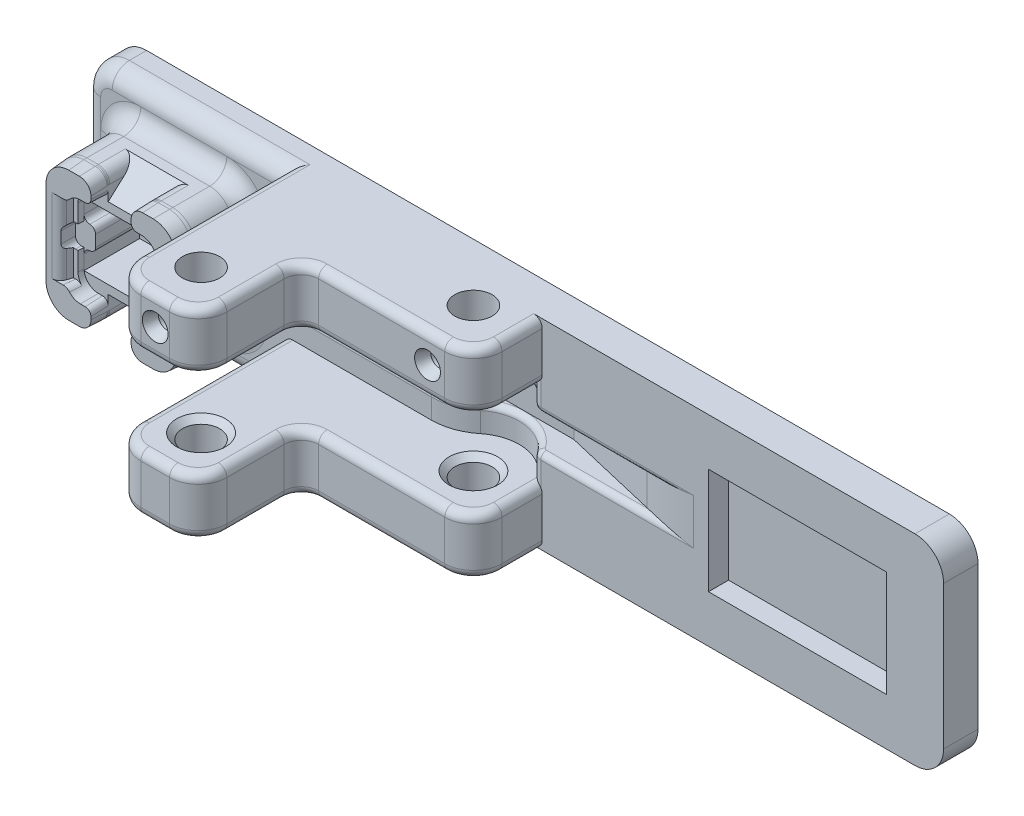
SolidWorks part; units mm, degrees
ref_plane "Top Plane" through (0, 0, 0) normal (0, 0, 1) x (1, 0, 0)
ref_plane "Right Plane" through (0, 0, 0) normal (0, 1, 0) x (1, 0, 0)
ref_plane "Front Plane" through (0, 0, 0) normal (1, 0, 0) x (0, 0, -1)
sketch "Sketch1" plane through (0, 0, 0) normal (0, 0, 1) x (1, 0, 0)
  line L0 (15, 2.5) -> (15, 6.45) construction
  line L1 (12.5, 15) -> (8.55, 15) construction
  line L2 (0, 6.45) -> (0, 2.5) construction
  line L3 (2.5, 0) -> (6.45, 0) construction
  line L4 (15, 2.5) -> (15, 6.45) construction
  line L5 (12.5, 15) -> (8.55, 15) construction
  line L6 (0, 6.45) -> (0, 2.5) construction
  line L7 (2.5, 0) -> (6.45, 0) construction
  line L8 (0, 0) -> (15, 15) construction
  line L9 (0, 0) -> (15, 0) construction
  line L10 (0, 0) -> (0, 15) construction
  line L11 (0, 15) -> (15, 15) construction
  line L12 (15, 0) -> (15, 15) construction
  line L14 (140, 25) -> (-10, 25)
  line L15 (140, 25) -> (140, -10)
  line L16 (140, -10) -> (-10, -10)
  line L17 (-10, 25) -> (-10, -10)
  circle A0 centre (14.2188, 11.3651) radius 0.5 construction
  circle A1 centre (14.2188, 3.6349) radius 0.5 construction
  circle A2 centre (7, 4) radius 0.5 construction
  circle A3 centre (4, 5.9999) radius 0.5 construction
  circle A4 centre (4, 9) radius 0.5 construction
  circle A5 centre (0.7812, 11.3651) radius 0.5 construction
  circle A6 centre (0.7812, 3.6349) radius 0.5 construction
  circle A7 centre (14.2188, 11.3651) radius 0.5
  circle A8 centre (14.2188, 3.6349) radius 0.5
  circle A9 centre (7, 4) radius 0.5
  circle A10 centre (4, 5.9999) radius 0.5
  circle A11 centre (4, 9) radius 0.5
  circle A12 centre (0.7812, 11.3651) radius 0.5
  circle A13 centre (0.7812, 3.6349) radius 0.5
  dimension "D1" = 10
  dimension "D2" = 10
  dimension "D3" = 10
  dimension "D4" = 125
extrude "Boss-Extrude1" add sketch "Sketch1" along normal blind 4 contours L15 L14 L17 L16
sketch "Sketch2" plane through (0, 0, 4) normal (0, 0, 1) x (1, 0, 0)
  line L0 (0, 0) -> (15, 15) construction
  line L1 (0, 15) -> (15, 15) construction
  line L2 (0, 15) -> (0, 0) construction
  line L3 (0, 0) -> (15, 0) construction
  line L4 (15, 15) -> (15, 0) construction
  line L5 (19, -4) -> (-4, -4)
  line L6 (19, -4) -> (19, 19)
  line L7 (19, 19) -> (-4, 19)
  line L8 (-4, -4) -> (-4, 19)
  line L9 (19, -4) -> (-4, 19) construction
  line L10 (19, 19) -> (-4, -4) construction
  line L11 (-0.2, 13) -> (-0.2, 9.5)
  line L13 (15.2, 13) -> (15.2, 9.5)
  line L15 (-0.2, 13) -> (15.2, 13)
  line L16 (-0.2, 2) -> (15.2, 2)
  line L17 (7.5, 0) -> (7.5, 2) construction
  line L18 (7.5, 13) -> (7.5, 15) construction
  line L19 (1.8, 7.5) -> (13.2, 7.5) construction
  line L20 (-0.2, 5.5) -> (-0.2, 2)
  line L21 (1.8, 5.5) -> (-0.2, 5.5)
  line L22 (1.8, 5.5) -> (1.8, 9.5)
  line L23 (1.8, 9.5) -> (-0.2, 9.5)
  line L25 (1.8, 5.5) -> (-0.2, 9.5) construction
  line L26 (1.8, 9.5) -> (-0.2, 5.5) construction
  line L27 (13.2, 5.5) -> (15.2, 5.5)
  line L28 (13.2, 5.5) -> (13.2, 9.5)
  line L29 (13.2, 9.5) -> (15.2, 9.5)
  line L31 (13.2, 5.5) -> (15.2, 9.5) construction
  line L32 (13.2, 9.5) -> (15.2, 5.5) construction
  line L33 (15.2, 5.5) -> (15.2, 2)
  line L34 (-0.2, 15.2) -> (-0.2, -0.2) construction
  line L35 (-0.2, 15.2) -> (15.2, 15.2) construction
  line L36 (15.2, 15.2) -> (15.2, -0.2) construction
  line L37 (-0.2, -0.2) -> (15.2, -0.2) construction
  point P6 (7.5, 7.5)
  point P25 (0.8, 7.5)
  point P32 (14.2, 7.5)
  point P37 (-4, -4)
  point P38 (7.5, 7.5)
  point P39 (-4, -4)
  point P40 (-4, 19)
  point P41 (7.5, 7.5)
  point P42 (15.2, 6.1932)
  point P43 (17.8091, 7.5)
  point P44 (13.2, 7.5)
  point P45 (0, 0)
  point P46 (0, 0)
  point P47 (7.5, 7.5)
  point P48 (-4, -4)
  dimension "D1" = 4
  dimension "D3" = 2
  dimension "D4" = 2
  dimension "D5" = 4
  dimension "D2" = 0.2
extrude "Boss-Extrude2" add sketch "Sketch2" along normal blind 9.7
sketch "Sketch3" plane through (0, 0, 13.7) normal (0, 0, 1) x (1, 0, 0)
  line L0 (15.2, 15.2) -> (15.2, -0.2)
  line L1 (0, 15) -> (15, 15) construction
  line L2 (0, 15) -> (0, 0) construction
  line L3 (0, 0) -> (15, 0) construction
  line L4 (15, 15) -> (15, 0) construction
  line L5 (-0.2, -0.2) -> (15.2, -0.2)
  line L6 (-0.2, 15.2) -> (-0.2, -0.2)
  line L7 (-0.2, 15.2) -> (15.2, 15.2)
  line L9 (-4, 19) -> (19, 19)
  line L10 (-4, 19) -> (-4, -4)
  line L11 (-4, -4) -> (19, -4)
  line L12 (19, 19) -> (19, -4)
  dimension "D1" = 0.2
extrude "Boss-Extrude3" add sketch "Sketch3" along normal blind 3 draft 3
sketch "Sketch4" plane through (19, 0, 0) normal (1, 0, 0) x (0, 0, -1)
  line L0 (-13.7, 7.5) -> (-4, 7.5) construction
  line L1 (-13.7, -4) -> (-13.7, 19) construction
  line L2 (-4, -4) -> (-4, 19) construction
  line L3 (-4, -10) -> (-4, 25) construction
  line L4 (-8, 2.5) -> (-4, 2.5)
  line L5 (-8, 2.5) -> (-8, 12.5)
  line L6 (-8, 12.5) -> (-4, 12.5)
  line L7 (-4, 2.5) -> (-4, 12.5)
  line L8 (-8, 2.5) -> (-4, 12.5) construction
  line L9 (-8, 12.5) -> (-4, 2.5) construction
  point P6 (-6, 7.5)
  dimension "D1" = 4
  dimension "D2" = 10
extrude "Cut-Extrude1" cut sketch "Sketch4" against normal up to next
chamfer "Chamfer1" distance 2 angle 45 1 edges at (13.2, 7.5, 8)
chamfer "Chamfer2" distance 3 angle 45 2 edges at (17.1, 12.5, 8) (17.1, 2.5, 8)
fillet "Fillet1" radius 1 4 edges at (1.8, 9.5, 8.85) (1.8, 5.5, 8.85) (13.2, 5.5, 11.85) (13.2, 9.5, 11.85)
fillet "Fillet2" radius 1 4 edges at (-0.2, 5.5, 8.85) (-0.2, 9.5, 8.85) (15.2, 9.5, 10.85) (15.2, 5.5, 10.85)
fillet "Fillet3" radius 2.5 4 edges at (-0.2786, -0.2786, 15.2) (15.2786, -0.2786, 15.2) (-0.2786, 15.2786, 15.2) (15.2786, 15.2786, 15.2)
fillet "Fillet4" radius 10 4 edges at (19, 7.5, 13.7) (7.5, -4, 13.7) (7.5, 19, 13.7) (-4, 7.5, 13.7)
fillet "Fillet5" radius 4 12 edges at (19, 19, 8.7191) (18.9966, 18.9966, 13.6999) (19, -4, 8.7191) (18.9966, -3.9966, 13.6999) (-4, -4, 8.7191) (-3.9966, -3.9966, 13.6999) (-4, 19, 8.7191) (-3.9966, 18.9966, 13.6999) (18.9145, 18.9145, 15.3308) (18.9145, -3.9145, 15.3308) (-3.9145, -3.9145, 15.3308) (-3.9145, 18.9145, 15.3308)
sketch "Sketch5" plane through (0, 0, 16.7) normal (0, 0, 1) x (1, 0, 0)
  line L0 (12.7034, 15.2) -> (2.2966, 15.2) construction
  line L1 (15, 19) -> (0, 19) construction
  line L2 (12.7034, 15.2) -> (2.2966, 15.2) construction
  line L3 (15, 19) -> (0, 19) construction
  line L4 (7.5, 15.2) -> (7.5, 19) construction
  line L5 (1.8, 7.5) -> (13.2, 7.5) construction
  line L6 (11, 15.2) -> (4, 15.2)
  line L7 (11, 15.2) -> (11, 19)
  line L8 (11, 19) -> (4, 19)
  line L9 (4, 15.2) -> (4, 19)
  line L10 (11, 15.2) -> (4, 19) construction
  line L11 (11, 19) -> (4, 15.2) construction
  line L12 (1.8, 8.5) -> (1.8, 6.5) construction
  line L13 (13.2, 6.5) -> (13.2, 8.5) construction
  line L14 (7.5, 13) -> (7.5, 2) construction
  line L15 (15.2, 13) -> (-0.2, 13) construction
  line L16 (-0.1824, 2) -> (15.1824, 2) construction
  line L17 (-0.2, 10.5) -> (-0.2, 4.5) construction
  line L18 (15.2, 4.5) -> (15.2, 10.5) construction
  line L19 (-0.2, 10.5) -> (-0.2, 4.5)
  line L20 (15.2, 4.5) -> (15.2, 10.5)
  line L21 (-0.2, 7.5) -> (-4, 7.5) construction
  line L22 (-4, 15) -> (-4, 0) construction
  line L23 (15.2, 7.5) -> (18.8428, 7.5) construction
  line L24 (18.8428, 0.1517) -> (18.8428, 14.8483) construction
  line L25 (16.7, 5.5) -> (15.2, 5.5)
  line L26 (-1.7, 5.5) -> (-0.2, 5.5)
  line L27 (-1.7, 5.5) -> (-1.7, 9.5)
  line L28 (-1.7, 9.5) -> (-0.2, 9.5)
  line L29 (-0.2, 5.5) -> (-0.2, 9.5)
  line L30 (-1.7, 5.5) -> (-0.2, 9.5) construction
  line L31 (-1.7, 9.5) -> (-0.2, 5.5) construction
  line L32 (15.2, 5.5) -> (15.2, 9.5)
  line L33 (16.7, 9.5) -> (15.2, 9.5)
  line L34 (16.7, 5.5) -> (16.7, 9.5)
  line L35 (11, -0.2) -> (4, -0.2)
  line L36 (11, -0.2) -> (11, -4)
  line L37 (11, -4) -> (4, -4)
  line L38 (4, -0.2) -> (4, -4)
  point P6 (7.5, 17.1)
  point P35 (-0.95, 7.5)
  dimension "D1" = 7
  dimension "D2" = 4
  dimension "D3" = 1.5
extrude "Cut-Extrude2" cut sketch "Sketch5" against normal up to surface (3 mm away) contours L7 L8 L9 L6 | L33 L32 L25 L34 | L36 L37 L38 L35 | L26 L29 L28 L27 up to face at (7.5, 14.3355, 13.7)
fillet "Fillet6" radius 1 4 edges at (16.7, 9.5, 15.2) (16.7, 5.5, 15.2) (-1.7, 5.5, 15.2) (-1.7, 9.5, 15.2)
fillet "Fillet7" radius 2 8 edges at (4, 18.9923, 13.8308) (4, -3.9923, 13.8308) (11, -3.9923, 13.8308) (11, 18.9923, 13.8308) (4, 18.9145, 15.3308) (4, -3.9145, 15.3308) (11, -3.9145, 15.3308) (11, 18.9145, 15.3308)
fillet "Fillet8" radius 1 4 edges at (4, -0.2786, 15.2) (11, -0.2786, 15.2) (4, 15.2786, 15.2) (11, 15.2786, 15.2)
sketch "Sketch6" plane through (11, 0, 0) normal (-1, 0, 0) x (0, 0, 1)
  line L0 (4, 19) -> (13.4381, 19)
  line L1 (4, 19) -> (13.4381, 19) construction
  line L2 (4, 13) -> (13.7, 13)
  line L3 (4, 13) -> (13.7, 13) construction
  line L4 (13.7, 13) -> (13.7, 14.5) construction
  line L5 (13.7, 14.5) -> (8.7191, 19)
  line L6 (13.7, 14.5) -> (13.7, 19)
  line L7 (13.7, 19) -> (8.7191, 19)
  line L8 (8, 9.5) -> (8, 5.5) construction
  line L9 (8, 9.5) -> (8, 5.5)
  line L10 (8, 7.5) -> (14.4347, 7.5) construction
  line L11 (13.7, 0.5) -> (8.7191, -4)
  line L12 (13.7, -4) -> (8.7191, -4)
  line L13 (13.7, 0.5) -> (13.7, -4)
  dimension "D1" = 1.5
extrude "Cut-Extrude3" cut sketch "Sketch6" along normal up to surface (7 mm away) contours L5 L7 L6 | L13 L12 L11 up to face at (4, 16.677, 14.9314)
fillet "Fillet9" radius 2 8 edges at (4, -3.9991, 13.5691) (11, -3.9991, 13.5691) (4, 18.9991, 13.5691) (11, 18.9991, 13.5691) (4, -4, 11.0786) (11, -4, 11.0786) (4, 19, 11.0786) (11, 19, 11.0786)
sketch "Sketch7" plane through (0, 0, 0) normal (0, 0, -1) x (-1, 0, 0)
  line L4 (10, -10) -> (10, 25)
  line L5 (10, 25) -> (-140, 25)
  line L6 (-140, 25) -> (-140, -10)
  line L7 (-140, -10) -> (10, -10)
  line L8 (10, -10) -> (10, 25)
  line L9 (10, 25) -> (-140, 25)
  line L10 (-140, 25) -> (-140, -10)
  line L11 (-140, -10) -> (10, -10)
  dimension "D1" = 0
extrude "Boss-Extrude4" add sketch "Sketch7" along normal blind 1 contours L8 L9 L10 L11
fillet "Fillet10" radius 5 4 edges at (-10, -10, 1.5) (-10, 25, 1.5) (140, 25, 1.5) (140, -10, 1.5)
sketch "Sketch8" plane through (0, 0, 4) normal (0, 0, 1) x (1, 0, 0)
  line L0 (-10, 7.5) -> (140, 7.5) construction
  line L1 (-10, 20) -> (-10, -5) construction
  line L2 (140, -5) -> (140, 20) construction
  line L4 (99, -1.75) -> (130, -1.75)
  line L5 (99, -1.75) -> (99, 16.75)
  line L6 (99, 16.75) -> (130, 16.75)
  line L7 (130, -1.75) -> (130, 16.75)
  line L8 (99, -1.75) -> (130, 16.75) construction
  line L9 (99, 16.75) -> (130, -1.75) construction
  point P6 (114.5, 7.5)
  point P11 (0, 0)
  dimension "D1" = 31
  dimension "D2" = 10
  dimension "D3" = 18.5
extrude "Cut-Extrude4" cut sketch "Sketch8" against normal blind 3.5 contours L5 L4 L7 L6
ref_plane "Middle" through (0, 7.5, 0) normal (0, -1, 0) x (-1, 0, 0)
sketch "Sketch11" plane through (0, -10, 0) normal (0, -1, 0) x (1, 0, 0)
  line L0 (-5, 4) -> (135, 4) construction
  line L1 (25, 4) -> (36.8212, 4)
  line L2 (25, 4) -> (25, 34)
  line L3 (25, 34) -> (40, 34)
  line L4 (40, 16) -> (40, 34)
  line L5 (19, 13.4381) -> (19, 4) construction
  line L6 (40, 16) -> (70, 16)
  line L8 (36.8212, 4) -> (70, 4)
  line L9 (70, 16) -> (70, 4)
  line L10 (32.5, 34) -> (32.5, 4) construction
  line L11 (62, 16) -> (62, 4) construction
  circle A0 centre (32.5, 26) radius 3.25
  circle A1 centre (62, 8) radius 3.25
  dimension "D7" = 6.5
  dimension "D8" = 8
  dimension "D1" = 30
  dimension "D2" = 15
  dimension "D3" = 30
  dimension "D4" = 12
  dimension "D5" = 6
  dimension "D6" = 8
  dimension "D9" = 8
extrude "Boss-Extrude6" add sketch "Sketch11" against normal blind 10
mirror "Mirror1" about plane through (0, 7.5, 0) normal (0, -1, 0) of "Boss-Extrude6"
fillet "Fillet11" radius 5 6 edges at (70, -5, 16) (70, 20, 16) (25, -5, 34) (40, -5, 34) (40, 20, 34) (25, 20, 34)
fillet "Fillet12" radius 3 2 edges at (40, 20, 16) (40, -5, 16)
sketch "Sketch12" plane through (0, 15, 0) normal (0, -1, 0) x (1, 0, 0)
  line L0 (65, 16) -> (43, 16) construction
  circle A0 centre (62, 8) radius 8
extrude "Cut-Extrude5" cut sketch "Sketch12" along normal up to surface (15 mm away) up to face at (65.25, 0, 8)
fillet "Fillet13" radius 10 1 edges at (55.0718, 7.5, 4)
fillet "Fillet14" radius 1.5 1 edges at (68.9282, 7.5, 4)
fillet "Fillet15" radius 1.5 38 edges at (70, 0, 7.5) (70, -10, 7.5) (70, 15, 7.5) (70, 25, 7.5) (54, -10, 16) (32.5, -10, 34) (25, -10, 16.5) (38.5355, -10, 32.5355) (26.4645, -10, 32.5355) (68.5355, -10, 14.5355) (54, 0, 16) (25, 0, 16.5) (32.5, 0, 34) (38.5355, 0, 32.5355) (26.4645, 0, 32.5355) (68.5355, 0, 14.5355) (54, 25, 16) (54, 15, 16) (25, 25, 16.5) (32.5, 25, 34) (26.4645, 25, 32.5355) (38.5355, 25, 32.5355) (68.5355, 25, 14.5355) (25, 15, 16.5) (32.5, 15, 34) (26.4645, 15, 32.5355) (38.5355, 15, 32.5355) (68.5355, 15, 14.5355) (40, 25, 24) (40, 15, 24) (40, 0, 24) (40, -10, 24) (40.8787, 25, 16.8787) (40.8787, 15, 16.8787) (40.8787, -10, 16.8787) (40.8787, 0, 16.8787) (69.0577, 15, 3.8328) (69.0577, 0, 3.8328)
fillet "Fillet16" radius 3 5 edges at (10.75, 25, 4) (-8.5355, 23.5355, 4) (10.75, -10, 4) (-8.5355, -8.5355, 4) (-10, 7.5, 4)
sketch "Sketch13" plane through (0, 7.5, 0) normal (0, -1, 0) x (-1, 0, 0)
  line L0 (0.2, -13.7) -> (0.7, -13.7) construction
  line L1 (0.2, -13.7) -> (0.7, -13.7) construction
  line L2 (0.7, -13.7) -> (-4.3, -13.7) construction
  line L3 (-4.3, -14.7) -> (-4.3, -47.4077)
  line L4 (1.0535, -14.7) -> (-4.3, -14.7)
  line L7 (0.7, -14.7) -> (-4.3, -14.7) construction
  arc A0 (-4.3, -47.4077) -> (0.7, -13.7) centre (-32.5, -26) ccw construction
  arc A1 (1.0535, -14.7) -> (-4.3, -47.4077) centre (-32.5, -26) cw
  dimension "D1" = 5
  dimension "D2" = 1
extrude "Cut-Extrude6" cut sketch "Sketch13" against normal mid plane 13
fillet "Fillet17" radius 1.5 2 edges at (-0.002, 14, 15.6935) (-0.002, 1, 15.6935)
fillet "Fillet18" radius 1.5 1 edges at (-1.662, 11.3866, 16.7)
fillet "Fillet19" radius 3 9 edges at (19, 1.25, 4) (17.8284, -2.8284, 4) (7.5, -4, 4) (-2.8284, -2.8284, 4) (-4, 7.5, 4) (-2.8284, 17.8284, 4) (7.5, 19, 4) (19, 13.75, 4) (17.8284, 17.8284, 4)
sketch "Sketch14" plane through (0, 7.5, 0) normal (0, -1, 0) x (-1, 0, 0)
  line L0 (-69.746, -4) -> (-99, -4)
  line L1 (-130, -4) -> (-140, -4)
  line L2 (-130, -4) -> (-140, -4)
  line L3 (-69.746, -4) -> (-91.746, -4)
  line L4 (-1.8, -4) -> (-50.6863, -4)
  line L5 (-25.6863, -4) -> (-50.6863, -4)
  line L6 (-91.746, -4) -> (-70.5229, 1)
  line L7 (5, 1) -> (-135, 1) construction
  line L8 (-70.5229, 1) -> (-54.9717, 1)
  line L9 (-54.9717, 1) -> (-25.6863, -4)
  arc A0 (-56.9717, -1.7778) -> (-50.6863, -4) centre (-50.6863, 6) ccw
  arc A1 (-56.9717, -1.7778) -> (-50.6863, -4) centre (-50.6863, 6) ccw
  arc A2 (-56.9717, -1.7778) -> (-68.5229, -3.3684) centre (-62, -8) ccw
  arc A3 (-56.9717, -1.7778) -> (-68.5229, -3.3684) centre (-62, -8) ccw
  arc A4 (-69.746, -4) -> (-68.5229, -3.3684) centre (-69.746, -2.5) ccw
  arc A5 (-69.746, -4) -> (-68.5229, -3.3684) centre (-69.746, -2.5) ccw
  point P16 (-69.746, 1)
  point P18 (-72.05, 1)
  point P19 (-69.746, 1)
  dimension "D1" = 25
  dimension "D2" = 2
  dimension "D3" = 22
  dimension "D4" = 2
extrude "Cut-Extrude7" cut sketch "Sketch14" against normal mid plane 6 contours L3 L6 L8 L9 L5 A1 A3 A5
fillet "Fillet20" radius 1 8 edges at (80.746, 10.5, 4) (69.0577, 10.5, 3.8328) (63.0913, 10.5, 0.0748) (54.0196, 10.5, 3.4281) (80.746, 4.5, 4) (69.0577, 4.5, 3.8328) (63.0913, 4.5, 0.0748) (54.0196, 4.5, 3.4281)
fillet "Fillet21" radius 40 5 edges at (91.746, 7.5, 4) (25.6863, 7.5, 4) (90.5027, 10.7929, 3.7071) (90.5027, 4.2071, 3.7071) (27.4018, 4.2071, 3.7071)
sketch "Sketch15" plane through (0, 0, -1) normal (0, 0, -1) x (-1, 0, 0)
  line L4 (5, 25) -> (-135, 25)
  line L5 (-140, 20) -> (-140, -5)
  line L6 (-135, -10) -> (5, -10)
  line L7 (10, -5) -> (10, 20)
  line L8 (5, 25) -> (-135, 25)
  line L9 (-140, 20) -> (-140, -5)
  line L10 (-135, -10) -> (5, -10)
  line L11 (10, -5) -> (10, 20)
  arc A4 (-135, 25) -> (-140, 20) centre (-135, 20) ccw
  arc A5 (-140, -5) -> (-135, -10) centre (-135, -5) ccw
  arc A6 (5, -10) -> (10, -5) centre (5, -5) ccw
  arc A7 (10, 20) -> (5, 25) centre (5, 20) ccw
  arc A8 (-135, 25) -> (-140, 20) centre (-135, 20) ccw
  arc A9 (-140, -5) -> (-135, -10) centre (-135, -5) ccw
  arc A10 (5, -10) -> (10, -5) centre (5, -5) ccw
  arc A11 (10, 20) -> (5, 25) centre (5, 20) ccw
  dimension "D1" = 0
extrude "Boss-Extrude7" add sketch "Sketch15" along normal blind 1
chamfer "Chamfer3" distance 1 angle 45 4 edges at (65.25, 15, 8) (35.75, 15, 26) (35.75, 0, 26) (65.25, 0, 8)
sketch "Sketch16" plane through (0, 0, 34) normal (0, 0, 1) x (1, 0, 0)
  line L0 (30, 20) -> (35, 20) construction
  line L1 (30, 23.5) -> (30, 16.5) construction
  line L2 (35, 16.5) -> (35, 23.5) construction
  line L3 (65.25, 25) -> (58.75, 25) construction
  line L4 (65.25, 25) -> (58.75, 25)
  line L5 (57.75, 15) -> (66.25, 15) construction
  line L6 (57.75, 15) -> (66.25, 15)
  line L7 (62, 25) -> (62, 15) construction
  circle A0 centre (32.5, 20) radius 1.5
  circle A1 centre (62, 20) radius 1.5
  dimension "D1" = 3
  dimension "D2" = 3
extrude "Cut-Extrude8" cut sketch "Sketch16" against normal up to next contours A0 | A1
chamfer "Chamfer4" distance 0.5 angle 60 7 edges at (14.7188, 11.3651, 4) (14.7188, 3.6349, 4) (7.5, 4, 4) (4.5, 5.9999, 4) (4.5, 9, 4) (1.2812, 11.3651, 4) (1.2812, 3.6349, 4)
chamfer "Chamfer5" distance 0.75 angle 70 2 edges at (34, 20, 34) (60.5, 20, 16)
